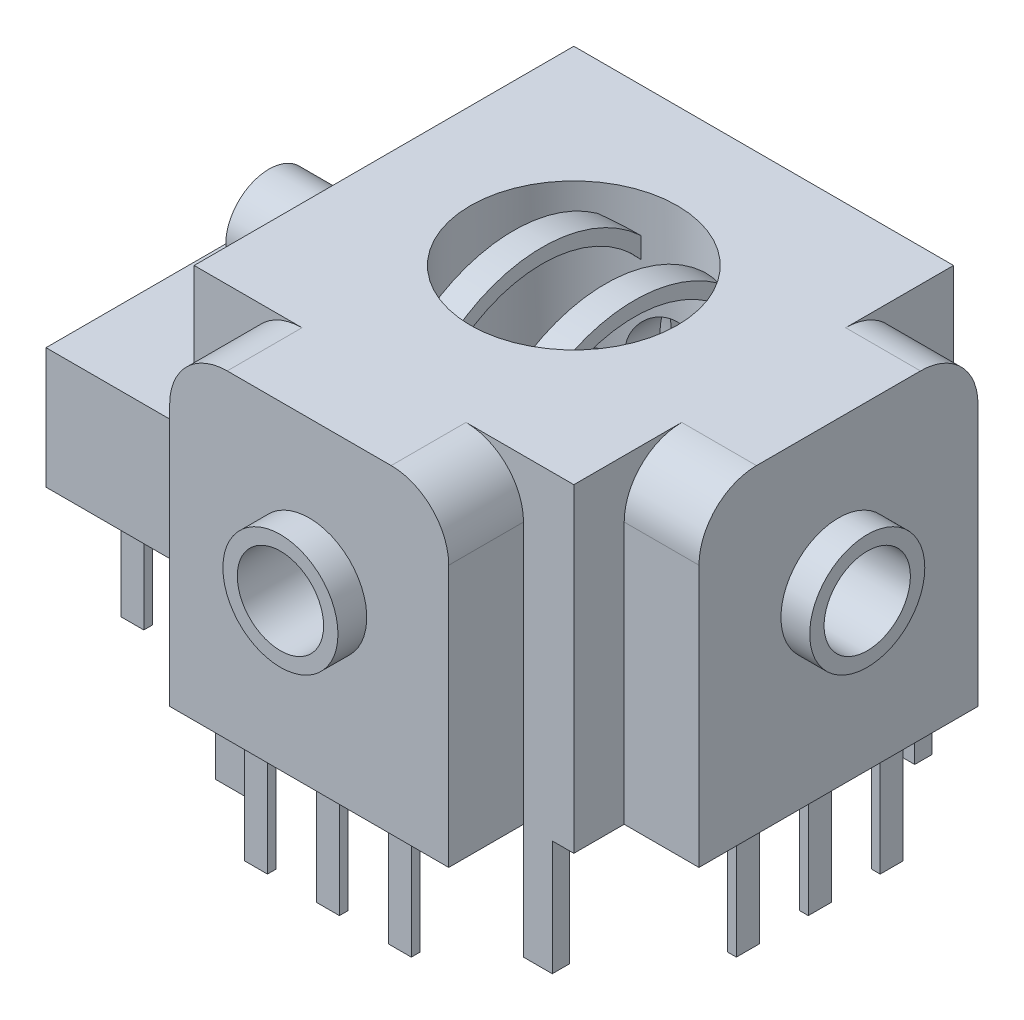
SolidWorks part; units mm, degrees
ref_plane "前视基准面" through (0, 0, 0) normal (0, 0, 1) x (1, 0, 0)
ref_plane "上视基准面" through (0, 0, 0) normal (0, 1, 0) x (1, 0, 0)
ref_plane "右视基准面" through (0, 0, 0) normal (1, 0, 0) x (0, 0, -1)
other "Configuration Table"
sketch "草图1" plane through (0, 0, 0) normal (0, 1, 0) x (1, 0, 0)
  line L0 (-3.45, 7.6) -> (3.45, 7.6) construction
  line L17 (-6.6, 6.6) -> (6.6, 6.6)
  line L18 (-6.6, 6.6) -> (-6.6, -6.6)
  line L23 (-6.6, -6.6) -> (6.6, -6.6)
  line L24 (6.6, 6.6) -> (6.6, -6.6)
  line L29 (-6.6, 4.75) -> (-13.6, 4.75)
  line L30 (-6.6, 4.75) -> (-6.6, -4.75)
  line L31 (-6.6, -4.75) -> (-13.6, -4.75)
  line L32 (-13.6, 4.75) -> (-13.6, -4.75)
  line L33 (6.6, 4.85) -> (9.2, 4.85)
  line L34 (6.6, 4.85) -> (6.6, -4.85)
  line L35 (6.6, -4.85) -> (9.2, -4.85)
  line L36 (9.2, 4.85) -> (9.2, -4.85)
  line L37 (-4.85, -6.6) -> (4.85, -6.6)
  line L38 (-4.85, -6.6) -> (-4.85, -9.2)
  line L39 (-4.85, -9.2) -> (4.85, -9.2)
  line L40 (4.85, -6.6) -> (4.85, -9.2)
  line L41 (-4.85, 6.6) -> (-3.45, 6.6)
  line L42 (-4.85, 6.6) -> (-4.85, 7.6)
  line L43 (-4.85, 7.6) -> (-3.45, 7.6)
  line L44 (-3.45, 6.6) -> (-3.45, 7.6)
  line L45 (3.45, 6.6) -> (4.85, 6.6)
  line L46 (3.45, 6.6) -> (3.45, 7.6)
  line L47 (3.45, 7.6) -> (4.85, 7.6)
  line L48 (4.85, 6.6) -> (4.85, 7.6)
  circle A0 centre (-10.1, 0) radius 1.75
  circle A1 centre (0, 0) radius 3.6
  point P4 (0, 6.6)
  point P6 (-6.6, 0)
  point P15 (0, -9.2)
  point P16 (9.2, 0)
  point P17 (-13.6, 0)
  point P28 (-10.1, 4.75)
  point P35 (0, 7.6)
  dimension "D8" = 3.5
  dimension "D12" = 7.2
  dimension "D1" = 22.8
  dimension "D2" = 13.2
  dimension "D3" = 15.8
  dimension "D4" = 15.8
  dimension "D5" = 9.7
  dimension "D6" = 9.7
  dimension "D7" = 9.5
  dimension "D9" = 1
  dimension "D10" = 1.4
extrude "凸台-拉伸1" add sketch "草图1" along normal blind 11.1 contours L23 L24 L17 L18 | L39 L40 L37 L38 | L35 L36 L33 L34
extrude "凸台-拉伸2" add sketch "草图1<7>" along normal blind 4.2 contours L32 L31 L30 L29
sketch "草图1<7>" plane through (0, 0, 0) normal (0, 1, 0) x (1, 0, 0) same geometry as "草图1"
extrude "凸台-拉伸3" add sketch "草图1<8>" along normal blind 5.2 contours A0
sketch "草图1<8>" plane through (0, 0, 0) normal (0, 1, 0) x (1, 0, 0) same geometry as "草图1"
sketch "草图2" plane through (-6.6, 0, 0) normal (-1, 0, 0) x (0, 0, 1)
  line L0 (1.75, 5.2) -> (-1.75, 5.2) construction
  circle A0 centre (0, 7.2) radius 1.5
  dimension "D1" = 3
  dimension "D2" = 2
extrude "凸台-拉伸4" add sketch "草图2" along normal blind 4 contours A0
extrude "凸台-拉伸5" add sketch "草图1<9>" along normal blind 1.8 contours L47 L48 L45 L46 | L43 L44 L41 L42
sketch "草图1<9>" plane through (0, 0, 0) normal (0, 1, 0) x (1, 0, 0) same geometry as "草图1"
sketch "草图3" plane through (9.2, 0, 0) normal (1, 0, 0) x (0, 0, -1)
  line L0 (-3.4035, 4.1) -> (10.0843, 4.1) construction
  line L1 (4.85, 11.1) -> (-4.85, 11.1) construction
  circle A0 centre (0, 6.1) radius 2
  circle A1 centre (0, 6.1) radius 1.5
  circle A2 centre (0, 6.1) radius 5
  dimension "D1" = 4
  dimension "D3" = 0.5
  dimension "D2" = 7
extrude "凸台-拉伸6" add sketch "草图3" along normal blind 1 contours A0 | A1
extrude "切除-拉伸1" cut sketch "草图3<3>" against normal blind 10 contours A1
sketch "草图3<3>" plane through (9.2, 0, 0) normal (1, 0, 0) x (0, 0, -1) same geometry as "草图3"
sketch "草图4" plane through (0, 0, 9.2) normal (0, 0, 1) x (1, 0, 0)
  line L0 (-18.2892, 4.1) -> (18.5063, 4.1) construction
  line L1 (-4.85, 11.1) -> (4.85, 11.1) construction
  circle A0 centre (0, 6.1) radius 2
  circle A1 centre (0, 6.1) radius 1.5
  dimension "D2" = 4
  dimension "D3" = 0.5
  dimension "D1" = 7
extrude "凸台-拉伸7" add sketch "草图4" along normal blind 1 contours A0 | A1
extrude "切除-拉伸2" cut sketch "草图4<3>" against normal through all contours A1
sketch "草图4<3>" plane through (0, 0, 9.2) normal (0, 0, 1) x (1, 0, 0) same geometry as "草图4"
extrude "切除-拉伸3" cut sketch "草图1<10>" against normal blind 5 from surface contours A1 starting at face at (2.6333, 11.1, 2.6333)
sketch "草图1<10>" plane through (0, 0, 0) normal (0, 1, 0) x (1, 0, 0) same geometry as "草图1"
sketch "草图5" plane through (0, 0, 0) normal (0, -1, 0) x (1, 0, 0)
  line L0 (-2.5, 8.4) -> (2.5, 8.4)
  line L1 (-2.9, 8.25) -> (-2.1, 8.25)
  line L2 (-2.9, 8.25) -> (-2.9, 8.55)
  line L3 (-2.9, 8.55) -> (-2.1, 8.55)
  line L4 (-2.1, 8.25) -> (-2.1, 8.55)
  line L5 (-2.9, 8.25) -> (-2.1, 8.55) construction
  line L6 (-2.9, 8.55) -> (-2.1, 8.25) construction
  line L7 (-0.4, 8.25) -> (0.4, 8.25)
  line L8 (-0.4, 8.25) -> (-0.4, 8.55)
  line L9 (-0.4, 8.55) -> (0.4, 8.55)
  line L10 (0.4, 8.25) -> (0.4, 8.55)
  line L11 (-0.4, 8.25) -> (0.4, 8.55) construction
  line L12 (-0.4, 8.55) -> (0.4, 8.25) construction
  line L13 (2.1, 8.25) -> (2.9, 8.25)
  line L14 (2.1, 8.25) -> (2.1, 8.55)
  line L15 (2.1, 8.55) -> (2.9, 8.55)
  line L16 (2.9, 8.25) -> (2.9, 8.55)
  line L17 (2.1, 8.25) -> (2.9, 8.55) construction
  line L18 (2.1, 8.55) -> (2.9, 8.25) construction
  line L19 (8.25, 2.9) -> (8.55, 2.9)
  line L20 (8.25, 2.9) -> (8.25, 2.1)
  line L21 (8.25, 2.1) -> (8.55, 2.1)
  line L22 (8.55, 2.9) -> (8.55, 2.1)
  line L23 (8.25, 2.9) -> (8.55, 2.1) construction
  line L24 (8.25, 2.1) -> (8.55, 2.9) construction
  line L25 (8.25, 0.4) -> (8.55, 0.4)
  line L26 (8.25, 0.4) -> (8.25, -0.4)
  line L27 (8.25, -0.4) -> (8.55, -0.4)
  line L28 (8.55, 0.4) -> (8.55, -0.4)
  line L29 (8.25, 0.4) -> (8.55, -0.4) construction
  line L30 (8.25, -0.4) -> (8.55, 0.4) construction
  line L31 (8.25, -2.1) -> (8.55, -2.1)
  line L32 (8.25, -2.1) -> (8.25, -2.9)
  line L33 (8.25, -2.9) -> (8.55, -2.9)
  line L34 (8.55, -2.1) -> (8.55, -2.9)
  line L35 (8.25, -2.1) -> (8.55, -2.9) construction
  line L36 (8.25, -2.9) -> (8.55, -2.1) construction
  line L37 (-12.4, 3.35) -> (-11.6, 3.35)
  line L38 (-12.4, 3.35) -> (-12.4, 3.05)
  line L39 (-12.4, 3.05) -> (-11.6, 3.05)
  line L40 (-11.6, 3.35) -> (-11.6, 3.05)
  line L41 (-12.4, 3.35) -> (-11.6, 3.05) construction
  line L42 (-12.4, 3.05) -> (-11.6, 3.35) construction
  line L43 (-8.2, 3.35) -> (-7.4, 3.35)
  line L44 (-8.2, 3.35) -> (-8.2, 3.05)
  line L45 (-8.2, 3.05) -> (-7.4, 3.05)
  line L46 (-7.4, 3.35) -> (-7.4, 3.05)
  line L47 (-8.2, 3.35) -> (-7.4, 3.05) construction
  line L48 (-8.2, 3.05) -> (-7.4, 3.35) construction
  line L49 (-12.4, -3.05) -> (-11.6, -3.05)
  line L50 (-12.4, -3.05) -> (-12.4, -3.35)
  line L51 (-12.4, -3.35) -> (-11.6, -3.35)
  line L52 (-11.6, -3.05) -> (-11.6, -3.35)
  line L53 (-12.4, -3.05) -> (-11.6, -3.35) construction
  line L54 (-12.4, -3.35) -> (-11.6, -3.05) construction
  line L55 (-8.2, -3.05) -> (-7.4, -3.05)
  line L56 (-8.2, -3.05) -> (-8.2, -3.35)
  line L57 (-8.2, -3.35) -> (-7.4, -3.35)
  line L58 (-7.4, -3.05) -> (-7.4, -3.35)
  line L59 (-8.2, -3.05) -> (-7.4, -3.35) construction
  line L60 (-8.2, -3.35) -> (-7.4, -3.05) construction
  line L61 (4.85, 6.6) -> (5.85, 6.6)
  line L62 (4.85, 6.6) -> (4.85, 6)
  line L63 (4.85, 6) -> (5.85, 6)
  line L64 (5.85, 6.6) -> (5.85, 6)
  line L65 (-4.85, 6.6) -> (-5.85, 6.6)
  line L66 (-4.85, 6.6) -> (-4.85, 6)
  line L67 (-4.85, 6) -> (-5.85, 6)
  line L68 (-5.85, 6.6) -> (-5.85, 6)
  line L69 (-4.85, -6.6) -> (-5.85, -6.6)
  line L70 (-4.85, -6.6) -> (-4.85, -6)
  line L71 (-4.85, -6) -> (-5.85, -6)
  line L72 (-5.85, -6.6) -> (-5.85, -6)
  line L73 (4.85, -6.6) -> (5.85, -6.6)
  line L74 (4.85, -6.6) -> (4.85, -6)
  line L75 (4.85, -6) -> (5.85, -6)
  line L76 (5.85, -6.6) -> (5.85, -6)
  line L77 (-4.85, 9.2) -> (4.85, 9.2) construction
  line L78 (8.4, 2.5) -> (8.4, -2.5)
  line L79 (9.2, -4.85) -> (9.2, 4.85) construction
  line L80 (-12, 3.2) -> (-12, -3.2)
  line L81 (-13.6, -4.75) -> (-13.6, 4.75) construction
  point P0 (-2.5, 8.4)
  point P5 (0, 8.4)
  point P10 (2.5, 8.4)
  point P15 (8.4, 2.5)
  point P20 (8.4, 0)
  point P25 (8.4, -2.5)
  point P30 (-12, 3.2)
  point P35 (-7.8, 3.2)
  point P45 (-7.8, -3.2)
  point P84 (-12, 0)
  point P89 (-12, -3.2)
  dimension "D1" = 5
  dimension "D2" = 0.3
  dimension "D3" = 0.8
  dimension "D4" = 0.8
  dimension "D5" = 0.8
  dimension "D6" = 6.4
  dimension "D7" = 4.2
  dimension "D8" = 6.2
  dimension "D9" = 0.6
  dimension "D10" = 1
extrude "凸台-拉伸8" add sketch "草图5" along normal blind 4 contours L50 L51 L52 L49 | L56 L57 L58 L55 | L38 L39 L40 L37 | L44 L45 L46 L43 | L68 L67 L66 L65 | L2 L3 L4 L1 | L9 L10 L7 L8 | L15 L16 L13 L14 | L62 L63 L64 L61 | L20 L21 L22 L19 | L26 L27 L28 L25 | L32 L33 L34 L31 | L71 L72 L69 L70 | L75 L76 L73 L74
fillet "圆角1" radius 2 4 edges at (7.9, 11.1, -4.85) (7.9, 11.1, 4.85) (4.85, 11.1, 7.9) (-4.85, 11.1, 7.9)
extrude "拉伸-薄壁1" add sketch "草图3<4>" along normal blind 1 from offset 8.1 thin contours A2 offset against normal yes thin type one direction reverse wall 0.5
sketch "草图3<4>" plane through (9.2, 0, 0) normal (1, 0, 0) x (0, 0, -1) same geometry as "草图3"
extrude "拉伸-薄壁2" add sketch "草图3<5>" along normal blind 1 from offset 11.3 thin contours A2 offset against normal yes thin type one direction reverse wall 0.5
sketch "草图3<5>" plane through (9.2, 0, 0) normal (1, 0, 0) x (0, 0, -1) same geometry as "草图3"
